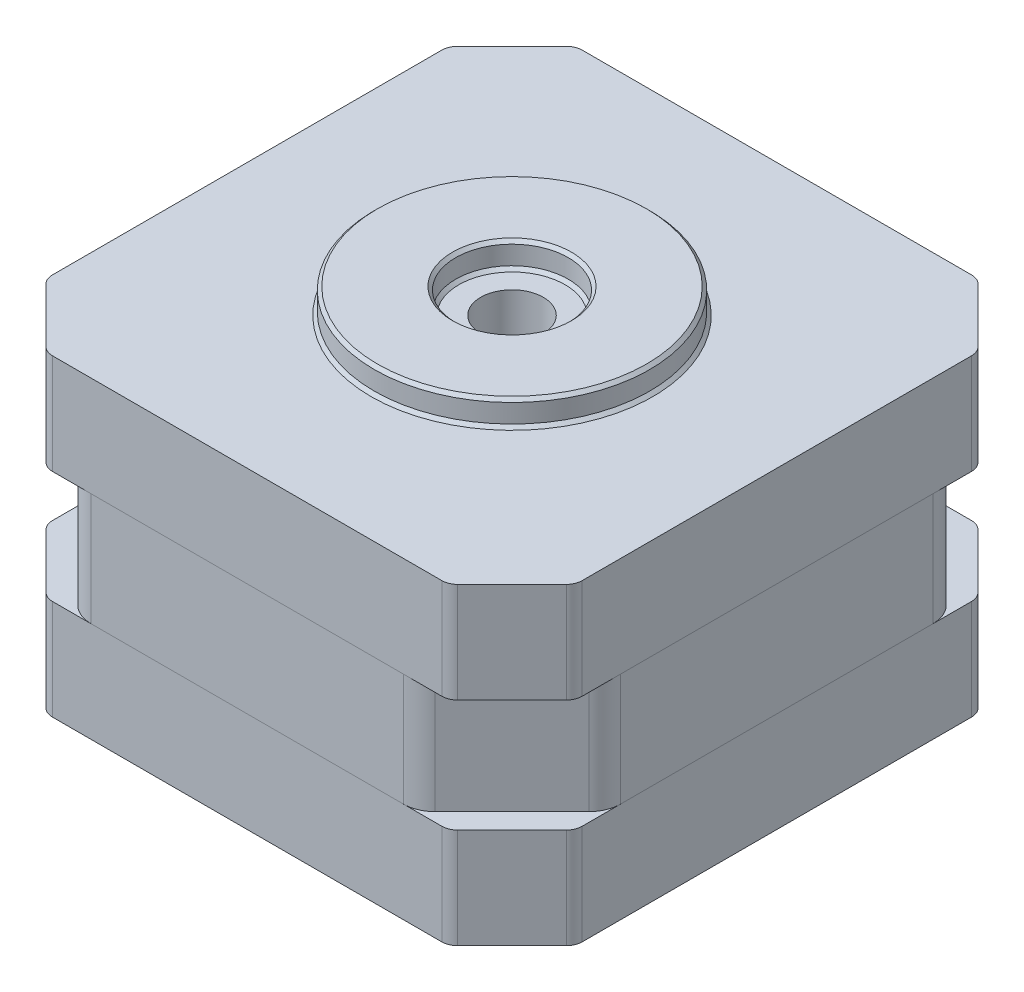
SolidWorks part; units mm, degrees
ref_plane "Front Plane" through (0, 0, 0) normal (0, 0, 1) x (1, 0, 0)
ref_plane "Top Plane" through (0, 0, 0) normal (0, 1, 0) x (1, 0, 0)
ref_plane "Right Plane" through (0, 0, 0) normal (1, 0, 0) x (0, 0, -1)
sketch "Sketch1" plane through (0, 0, 0) normal (0, 1, 0) x (1, 0, 0)
  line L1 (-21.15, 21.15) -> (21.15, 21.15)
  line L2 (-21.15, 21.15) -> (-21.15, -21.15)
  line L3 (-21.15, -21.15) -> (21.15, -21.15)
  line L4 (21.15, 21.15) -> (21.15, -21.15)
  line L5 (-21.15, 21.15) -> (21.15, -21.15) construction
  line L6 (-21.15, -21.15) -> (21.15, 21.15) construction
  point P0 (0, 0)
  dimension "D1" = 42.3
extrude "Boss-Extrude1" add sketch "Sketch1" along normal blind 8.001
chamfer "Chamfer1" distance 5.08 angle 45 4 edges at (-21.15, 4.0005, 21.15) (-21.15, 4.0005, -21.15) (21.15, 4.0005, -21.15) (21.15, 4.0005, 21.15)
sketch "Sketch2" plane through (0, 8.001, 0) normal (0, 1, 0) x (1, 0, 0)
  line L0 (16.07, 21.15) -> (-16.07, 21.15) construction
  line L1 (-21.15, -21.15) -> (21.15, -21.15)
  line L2 (-21.15, -21.15) -> (-21.15, 21.15)
  line L3 (-21.15, 21.15) -> (21.15, 21.15)
  line L4 (21.15, -21.15) -> (21.15, 21.15)
  line L5 (-21.15, -21.15) -> (21.15, 21.15) construction
  line L6 (-21.15, 21.15) -> (21.15, -21.15) construction
  line L7 (21.15, -16.07) -> (21.15, 16.07) construction
  point P0 (0, 0)
extrude "Boss-Extrude2" add sketch "Sketch2" along normal blind 8.9916 separate body
chamfer "Chamfer3" distance 7.62 angle 45 4 edges at (-21.15, 12.4968, -21.15) (-21.15, 12.4968, 21.15) (21.15, 12.4968, 21.15) (21.15, 12.4968, -21.15)
fillet "Fillet1" radius 2.54 8 edges at (-21.15, 12.4968, -13.53) (-13.53, 12.4968, -21.15) (13.53, 12.4968, -21.15) (21.15, 12.4968, -13.53) (21.15, 12.4968, 13.53) (13.53, 12.4968, 21.15) (-13.53, 12.4968, 21.15) (-21.15, 12.4968, 13.53)
fillet "Fillet2" radius 1.27 8 edges at (-21.15, 4.0005, -16.07) (-16.07, 4.0005, -21.15) (16.07, 4.0005, -21.15) (21.15, 4.0005, -16.07) (21.15, 4.0005, 16.07) (16.07, 4.0005, 21.15) (-16.07, 4.0005, 21.15) (-21.15, 4.0005, 16.07)
sketch "Sketch3" plane through (0, 16.9926, 0) normal (0, 1, 0) x (1, 0, 0)
  line L0 (21.15, -12.4779) -> (21.15, 12.4779) construction
  line L1 (-21.15, 21.15) -> (21.15, 21.15)
  line L2 (-21.15, 21.15) -> (-21.15, -21.15)
  line L3 (-21.15, -21.15) -> (21.15, -21.15)
  line L4 (21.15, 21.15) -> (21.15, -21.15)
  line L5 (-21.15, 21.15) -> (21.15, -21.15) construction
  line L6 (-21.15, -21.15) -> (21.15, 21.15) construction
  line L7 (12.4779, 21.15) -> (-12.4779, 21.15) construction
  point P0 (0, 0)
extrude "Boss-Extrude3" add sketch "Sketch3" along normal blind 8.001 separate body
chamfer "Chamfer4" distance 5.08 angle 45 4 edges at (-21.15, 20.9931, 21.15) (-21.15, 20.9931, -21.15) (21.15, 20.9931, -21.15) (21.15, 20.9931, 21.15)
fillet "Fillet3" radius 1.27 8 edges at (-21.15, 20.9931, -16.07) (-16.07, 20.9931, -21.15) (16.07, 20.9931, -21.15) (21.15, 20.9931, -16.07) (21.15, 20.9931, 16.07) (16.07, 20.9931, 21.15) (-16.07, 20.9931, 21.15) (-21.15, 20.9931, 16.07)
sketch "Sketch4" plane through (0, 24.9936, 0) normal (0, 1, 0) x (1, 0, 0)
  circle A0 centre (0, 0) radius 10.9982
  circle A1 centre (0, 0) radius 4.4958
  dimension "D1" = 21.9964
  dimension "D2" = 8.9916
extrude "Boss-Extrude4" add sketch "Sketch4" along normal blind 2
chamfer "Chamfer5" distance 0.254 angle 45 4 edges at (0, 26.9936, 10.9982) (0, 24.9936, 10.9982) (0, 24.9936, 4.4958) (0, 26.9936, 4.4958)
sketch "Sketch5" plane through (0, 24.9936, 0) normal (0, 1, 0) x (1, 0, 0)
  circle A0 centre (0, 0) radius 2.5019
  dimension "D1" = 5.0038
extrude "Cut-Extrude1" cut sketch "Sketch5" against normal through all
